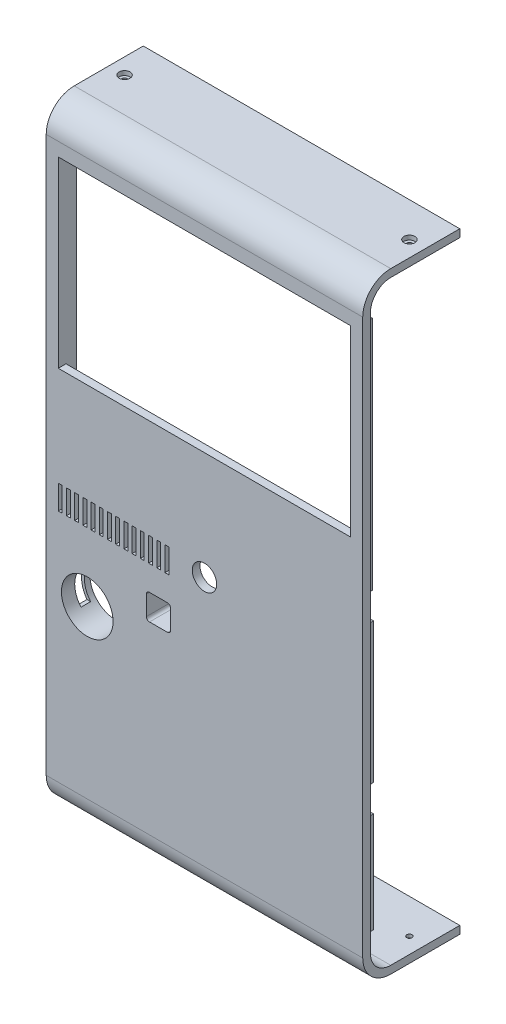
SolidWorks part; units mm, degrees
ref_plane "Alzado" through (0, 0, 0) normal (0, 0, 1) x (1, 0, 0)
ref_plane "Planta" through (0, 0, 0) normal (0, 1, 0) x (1, 0, 0)
ref_plane "Vista lateral" through (0, 0, 0) normal (1, 0, 0) x (0, 0, -1)
sketch "Croquis2" plane through (0, 0, 0) normal (1, 0, 0) x (0, 0, -1)
  line L0 (37, 0) -> (37, -3.2)
  line L1 (8.4, 0) -> (37, 0)
  line L2 (0, 8.4) -> (0, 238.3)
  line L3 (8.4, 246.7) -> (37, 246.7)
  line L5 (37, 246.7) -> (37, 249.9)
  line L6 (37, -3.2) -> (8.4, -3.2)
  line L7 (37, 249.9) -> (8.4, 249.9)
  line L8 (-3.2, 238.3) -> (-3.2, 8.4)
  arc A0 (8.4, 246.7) -> (0, 238.3) centre (8.4, 238.3) ccw
  arc A1 (0, 8.4) -> (8.4, 0) centre (8.4, 8.4) ccw
  arc A4 (8.4, 249.9) -> (-3.2, 238.3) centre (8.4, 238.3) ccw
  arc A5 (-3.2, 8.4) -> (8.4, -3.2) centre (8.4, 8.4) ccw
  point P9 (0, 0)
  dimension "D3" = 8.4
  dimension "D6" = 3.2
  dimension "D5" = 11.6
  dimension "D1" = 246.7
  dimension "D2" = 37
  dimension "D4" = 3.2
extrude "Saliente-Extruir1" add sketch "Croquis2" along normal blind 131.1
sketch "Croquis3" plane through (0, 249.9, 0) normal (0, 1, 0) x (1, 0, 0)
  line L0 (131.1, 37) -> (0, 37) construction
  line L1 (0, 37) -> (0, 8.4) construction
  line L2 (65.55, 37) -> (65.55, 8.4) construction
  line L4 (131.1, 8.4) -> (0, 8.4) construction
  circle A0 centre (6.55, 22.7) radius 1.1
  circle A1 centre (124.55, 22.7) radius 1.1
  dimension "D3" = 2.2
  dimension "D1" = 14.3
  dimension "D2" = 6.55
extrude "Cortar-Extruir1" cut sketch "Croquis3" against normal through all
sketch "Croquis4" plane through (0, 0, 3.2) normal (0, 0, 1) x (1, 0, 0)
  line L0 (131.1, 8.4) -> (0, 8.4) construction
  line L1 (0, 249.9) -> (0, 246.7) construction
  line L2 (65.55, 238.3) -> (65.55, 8.4) construction
  line L4 (5, 232.7) -> (126.1, 232.7)
  line L5 (126.1, 232.7) -> (126.1, 156.9)
  line L6 (126.1, 156.9) -> (5, 156.9)
  line L7 (5, 156.9) -> (5, 232.7)
  line L8 (0, 238.3) -> (0, 8.4) construction
  line L9 (131.1, 238.3) -> (0, 238.3) construction
  line L10 (8.4, 115.7) -> (8.4, 105.7)
  line L11 (41.5, 84.8) -> (51.5, 84.8)
  line L12 (41.5, 84.8) -> (41.5, 95.4)
  line L13 (41.5, 95.4) -> (51.5, 95.4)
  line L14 (51.5, 84.8) -> (51.5, 95.4)
  line L15 (5, 115.7) -> (6.6, 115.7)
  line L16 (5, 115.7) -> (5, 105.7)
  line L17 (5, 105.7) -> (6.6, 105.7)
  line L18 (6.6, 115.7) -> (6.6, 105.7)
  line L19 (8.4, 115.7) -> (10, 115.7)
  line L20 (10, 115.7) -> (10, 105.7)
  line L21 (8.4, 105.7) -> (10, 105.7)
  line L22 (11.8, 115.7) -> (11.8, 105.7)
  line L23 (11.8, 115.7) -> (13.4, 115.7)
  line L24 (13.4, 115.7) -> (13.4, 105.7)
  line L25 (11.8, 105.7) -> (13.4, 105.7)
  line L26 (15.2, 115.7) -> (15.2, 105.7)
  line L27 (15.2, 115.7) -> (16.8, 115.7)
  line L28 (16.8, 115.7) -> (16.8, 105.7)
  line L29 (15.2, 105.7) -> (16.8, 105.7)
  line L30 (18.6, 115.7) -> (18.6, 105.7)
  line L31 (18.6, 115.7) -> (20.2, 115.7)
  line L32 (20.2, 115.7) -> (20.2, 105.7)
  line L33 (18.6, 105.7) -> (20.2, 105.7)
  line L34 (22, 115.7) -> (22, 105.7)
  line L35 (22, 115.7) -> (23.6, 115.7)
  line L36 (23.6, 115.7) -> (23.6, 105.7)
  line L37 (22, 105.7) -> (23.6, 105.7)
  line L38 (25.4, 115.7) -> (25.4, 105.7)
  line L39 (25.4, 115.7) -> (27, 115.7)
  line L40 (27, 115.7) -> (27, 105.7)
  line L41 (25.4, 105.7) -> (27, 105.7)
  line L42 (28.8, 115.7) -> (28.8, 105.7)
  line L43 (28.8, 115.7) -> (30.4, 115.7)
  line L44 (30.4, 115.7) -> (30.4, 105.7)
  line L45 (28.8, 105.7) -> (30.4, 105.7)
  line L46 (32.2, 115.7) -> (32.2, 105.7)
  line L47 (32.2, 115.7) -> (33.8, 115.7)
  line L48 (33.8, 115.7) -> (33.8, 105.7)
  line L49 (32.2, 105.7) -> (33.8, 105.7)
  line L50 (35.6, 115.7) -> (35.6, 105.7)
  line L51 (35.6, 115.7) -> (37.2, 115.7)
  line L52 (37.2, 115.7) -> (37.2, 105.7)
  line L53 (35.6, 105.7) -> (37.2, 105.7)
  line L54 (39, 115.7) -> (39, 105.7)
  line L55 (39, 115.7) -> (40.6, 115.7)
  line L56 (40.6, 115.7) -> (40.6, 105.7)
  line L57 (39, 105.7) -> (40.6, 105.7)
  line L58 (42.4, 115.7) -> (42.4, 105.7)
  line L59 (42.4, 115.7) -> (44, 115.7)
  line L60 (44, 115.7) -> (44, 105.7)
  line L61 (42.4, 105.7) -> (44, 105.7)
  line L62 (45.8, 115.7) -> (45.8, 105.7)
  line L63 (45.8, 115.7) -> (47.4, 115.7)
  line L64 (47.4, 115.7) -> (47.4, 105.7)
  line L65 (45.8, 105.7) -> (47.4, 105.7)
  line L66 (49.2, 115.7) -> (49.2, 105.7)
  line L67 (49.2, 115.7) -> (50.8, 115.7)
  line L68 (50.8, 115.7) -> (50.8, 105.7)
  line L69 (49.2, 105.7) -> (50.8, 105.7)
  circle A0 centre (17, 77.4) radius 10.7
  circle A1 centre (65.55, 112.2) radius 5.07
  point P0 (5, 232.7)
  point P9 (126.1, 232.7)
  dimension "D6" = 21.4
  dimension "D16" = 10.14
  dimension "D2" = 121.1
  dimension "D3" = 75.8
  dimension "D4" = 17
  dimension "D5" = 169.3
  dimension "D7" = 24.5
  dimension "D8" = 151.3
  dimension "D9" = 10
  dimension "D10" = 10.6
  dimension "D11" = 131
  dimension "D12" = 10
  dimension "D13" = 1.6
  dimension "D14" = 5
  dimension "D17" = 134.5
  dimension "D18" = 14
  dimension "D15" = 14
extrude "Cortar-Extruir2" cut sketch "Croquis4" against normal through all
sketch "Croquis7" plane through (0, 0, 0) normal (0, 0, -1) x (-1, 0, 0)
  line L5 (-127.46, 124) -> (-127.96, 124)
  line L10 (-126.1, 232.7) -> (-127.46, 232.7)
  line L11 (-126.1, 232.7) -> (-126.1, 134.7)
  line L12 (-126.1, 134.7) -> (-127.46, 134.7)
  line L13 (-127.46, 232.7) -> (-127.46, 134.7)
  line L14 (-5, 232.7) -> (-3.64, 232.7)
  line L15 (-5, 232.7) -> (-5, 134.7)
  line L16 (-5, 134.7) -> (-3.64, 134.7)
  line L17 (-3.64, 232.7) -> (-3.64, 134.7)
  line L18 (-127.46, 124) -> (-126.1, 124)
  line L20 (-127.46, 66) -> (-126.1, 66)
  line L21 (-126.1, 124) -> (-126.1, 66)
  line L22 (-3.64, 124) -> (-5, 124)
  line L24 (-3.64, 66) -> (-5, 66)
  line L25 (-5, 124) -> (-5, 66)
  line L27 (-127.46, 66) -> (-127.96, 66)
  line L28 (-127.96, 124) -> (-127.96, 66)
  line L29 (-3.64, 124) -> (-3.14, 124)
  line L31 (-3.64, 66) -> (-3.14, 66)
  line L32 (-3.14, 124) -> (-3.14, 66)
  line L33 (-126.1, 54.76) -> (-127.96, 54.76)
  line L34 (-126.1, 54.76) -> (-126.1, 13.16)
  line L35 (-126.1, 13.16) -> (-127.96, 13.16)
  line L36 (-127.96, 54.76) -> (-127.96, 13.16)
  line L37 (-5, 54.76) -> (-3.14, 54.76)
  line L38 (-5, 54.76) -> (-5, 13.16)
  line L39 (-5, 13.16) -> (-3.14, 13.16)
  line L40 (-3.14, 54.76) -> (-3.14, 13.16)
  dimension "D1" = 1.36
  dimension "D2" = 98
  dimension "D3" = 10.7
  dimension "D4" = 58
  dimension "D5" = 0.5
  dimension "D6" = 0.5
  dimension "D7" = 11.24
  dimension "D8" = 1.36
  dimension "D9" = 1.36
  dimension "D10" = 0.5
  dimension "D11" = 1.36
  dimension "D12" = 41.6
extrude "Saliente-Extruir2" add sketch "Croquis7" along normal blind 4.4
sketch "Croquis8" plane through (0, 249.9, 0) normal (0, 1, 0) x (1, 0, 0)
  circle A0 centre (6.55, 22.7) radius 2.27
  circle A1 centre (124.55, 22.7) radius 2.27
  dimension "D1" = 4.54
extrude "Cortar-Extruir3" cut sketch "Croquis8" against normal blind 1.8
sketch "Croquis9" plane through (0, -3.2, 0) normal (0, -1, 0) x (1, 0, 0)
  circle A0 centre (124.55, -22.7) radius 2.27
  circle A1 centre (6.55, -22.7) radius 2.27
  dimension "D1" = 4.54
extrude "Cortar-Extruir4" cut sketch "Croquis9" against normal blind 1.8
sketch "Croquis10" plane through (0, 0, 0) normal (0, 0, -1) x (-1, 0, 0)
  line L0 (-41.5, 84.8) -> (-51.5, 84.8) construction
  line L1 (-51.5, 95.4) -> (-41.5, 95.4)
  line L2 (-51.5, 95.4) -> (-51.5, 84.8)
  line L3 (-51.5, 84.8) -> (-41.5, 84.8)
  line L4 (-41.5, 95.4) -> (-41.5, 84.8)
  line L5 (-52.7, 96.6) -> (-40.3, 96.6)
  line L6 (-40.3, 96.6) -> (-40.3, 83.6)
  line L7 (-40.3, 83.6) -> (-52.7, 83.6)
  line L8 (-52.7, 83.6) -> (-52.7, 96.6)
  line L9 (-41.5, 95.4) -> (-41.5, 84.8) construction
  circle A0 centre (-17, 77.4) radius 11.9
  circle A1 centre (-17, 77.4) radius 10.7 construction
  circle A2 centre (-17, 77.4) radius 10.7
  dimension "D1" = 1.2
  dimension "D2" = 1.2
  dimension "D3" = 1.2
  dimension "D4" = 1.2
  dimension "D5" = 1.2
extrude "Saliente-Extruir4" add sketch "Croquis10" along normal blind 8.6
fillet "Redondeo2" radius 1.28 4 edges at (51.5, 84.8, -2.7) (51.5, 95.4, -2.7) (41.5, 95.4, -2.7) (41.5, 84.8, -2.7)
ref_plane "Plano1" through (-10, 0, 0) normal (-1, 0, 0) x (0, 0, 1)
sketch "Croquis11" plane through (-10, 0, 0) normal (-1, 0, 0) x (0, 0, 1)
  line L0 (-8.6, 77.4) -> (0, 77.4) construction
  line L1 (-8.6, 89.3) -> (-8.6, 65.5) construction
  line L4 (-6.3, 70.4) -> (-2.3, 70.4)
  line L5 (-6.3, 70.4) -> (-6.3, 84.4)
  line L6 (-6.3, 84.4) -> (-2.3, 84.4)
  line L7 (-2.3, 70.4) -> (-2.3, 84.4)
  line L8 (-6.3, 70.4) -> (-2.3, 84.4) construction
  line L9 (-6.3, 84.4) -> (-2.3, 70.4) construction
  line L10 (0, 8.4) -> (0, 238.3) construction
  point P4 (0, 0)
  point P5 (0, 0)
  point P6 (-4.3, 77.4)
  dimension "D1" = 4
  dimension "D2" = 14
extrude "Cortar-Extruir5" cut sketch "Croquis11" against normal up to surface (18.9074 mm away) up to face at (27.7, 77.4, 3.2)
sketch "Croquis13" plane through (0, 0, -8.6) normal (0, 0, -1) x (-1, 0, 0)
  line L0 (-50.22, 95.4) -> (-42.78, 95.4)
  line L1 (-50.22, 84.8) -> (-42.78, 84.8)
  line L2 (-41.5, 86.08) -> (-41.5, 94.12)
  line L3 (-51.5, 86.08) -> (-51.5, 94.12)
  line L4 (-52.7, 96.6) -> (-52.7, 83.6)
  line L5 (-52.7, 83.6) -> (-40.3, 83.6)
  line L6 (-40.3, 83.6) -> (-40.3, 96.6)
  line L7 (-40.3, 96.6) -> (-52.7, 96.6)
  line L8 (-52.7, 96.6) -> (-52.7, 83.6)
  line L9 (-52.7, 83.6) -> (-40.3, 83.6)
  line L10 (-40.3, 83.6) -> (-40.3, 96.6)
  line L11 (-40.3, 96.6) -> (-52.7, 96.6)
  circle A0 centre (-50.22, 94.12) radius 1.28
  circle A1 centre (-50.22, 86.08) radius 1.28
  circle A2 centre (-42.78, 86.08) radius 1.28
  circle A3 centre (-42.78, 94.12) radius 1.28
  line M5 (-52.7, 96.6) -> (-52.7, 83.6)
  line M6 (-52.7, 83.6) -> (-40.3, 83.6)
  line M7 (-40.3, 83.6) -> (-40.3, 96.6)
  line M8 (-40.3, 96.6) -> (-52.7, 96.6)
  line M9 (-51.5, 86.08) -> (-51.5, 94.12)
  arc M10 (-51.5, 94.12) -> (-50.22, 95.4) centre (-50.22, 94.12) cw
  line M11 (-50.22, 95.4) -> (-42.78, 95.4)
  arc M12 (-42.78, 95.4) -> (-41.5, 94.12) centre (-42.78, 94.12) cw
  line M13 (-41.5, 94.12) -> (-41.5, 86.08)
  arc M14 (-41.5, 86.08) -> (-42.78, 84.8) centre (-42.78, 86.08) cw
  line M15 (-42.78, 84.8) -> (-50.22, 84.8)
  arc M16 (-50.22, 84.8) -> (-51.5, 86.08) centre (-50.22, 86.08) cw
  dimension "D1" = 0
extrude "Saliente-Extruir6" add sketch "Croquis13" along normal blind 1 contours M8 M5 M6 M7 M16 M9 M10 M11 M12 M13 M14 M15 region at (46.5, 96.4203, -8.6)
sketch "Croquis14" plane through (0, 0, 0) normal (0, 0, -1) x (-1, 0, 0)
  line L0 (-65.55, 112.2) -> (-65.55, 74.9205) construction
  circle A0 centre (-65.55, 87.5) radius 1.5
  circle A1 centre (-65.55, 87.5) radius 2.8
  dimension "D2" = 3
  dimension "D3" = 5.6
  dimension "D1" = 24.7
extrude "Saliente-Extruir7" add sketch "Croquis14" along normal blind 8.4
fillet "Redondeo3" radius 1.28 1 edges at (68.35, 87.5, 0)
sketch "Croquis17" plane through (127.46, 0, 0) normal (1, 0, 0) x (0, 0, -1)
  line L0 (4.4, 232.7) -> (4.4, 134.7) construction
  line L1 (0, 232.7) -> (4.4, 232.7)
  line L2 (0, 232.7) -> (0, 232.3)
  line L3 (0, 232.3) -> (4.4, 232.3)
  line L4 (4.4, 232.7) -> (4.4, 232.3)
  dimension "D1" = 0.4
extrude "Cortar-Extruir6" cut sketch "Croquis17" against normal through all
fillet "Redondeo4" radius 1.6 2 edges at (52.7, 90.1, 0) (40.3, 90.1, 0)
sketch "Croquis19" plane through (0, 0, 0) normal (0, 0, -1) x (-1, 0, 0)
  line L5 (-17, 65.5) -> (-17, 77.4) construction
  line L18 (-17, 77.4) -> (-17, 89.3) construction
  circle A2 centre (-17, 77.4) radius 11.9 construction
  circle A3 centre (-17, 89.3) radius 1.12
  circle A4 centre (-17, 65.5) radius 1.12
  dimension "D1" = 2.24
extrude "Saliente-Extruir8" add sketch "Croquis19" along normal up to surface (8.6 mm away) up to face at (5.1, 77.4, -8.6)
fillet "Redondeo5" radius 1 1 edges at (28.9, 77.4, 0)
